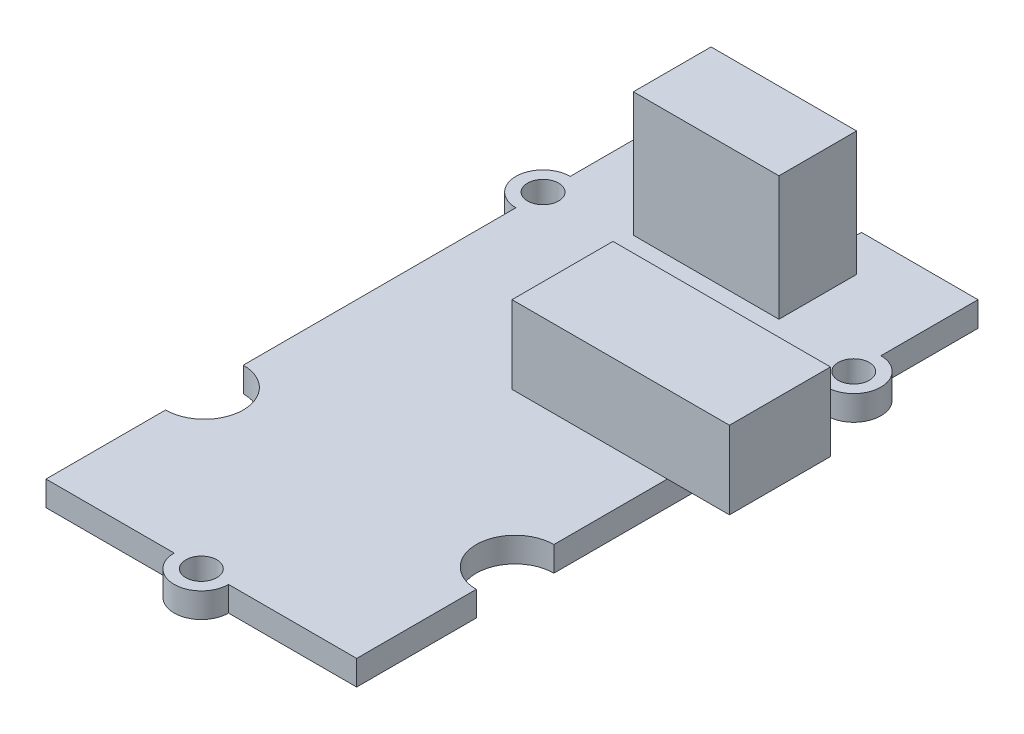
SolidWorks part; units mm, degrees
ref_plane "Front Plane" through (0, 0, 0) normal (0, 0, 1) x (1, 0, 0)
ref_plane "Top Plane" through (0, 0, 0) normal (0, 1, 0) x (1, 0, 0)
ref_plane "Right Plane" through (0, 0, 0) normal (1, 0, 0) x (0, 0, -1)
sketch "Sketch1" plane through (0, 0, 0) normal (0, 1, 0) x (1, 0, 0)
  line L0 (0, 20) -> (0, -20) construction
  line L1 (-10, -20) -> (10, -20)
  line L2 (-10, -20) -> (-10, 20)
  line L3 (-10, 20) -> (10, 20)
  line L4 (10, -20) -> (10, 20)
  line L5 (-10, -20) -> (10, 20) construction
  line L6 (-10, 20) -> (10, -20) construction
  circle A0 centre (10, 12) radius 1
  circle A1 centre (10, 12) radius 1.75
  circle A2 centre (-10, 12) radius 1.75
  circle A3 centre (-10, 12) radius 1
  circle A4 centre (0, -20) radius 1
  circle A5 centre (0, -20) radius 1.75
  circle A6 centre (10, -9.8) radius 2.5
  circle A7 centre (-10, -9.8) radius 2.5
  circle A8 centre (0, 20) radius 2.5
  point P0 (0, 0)
  point P25 (0, 0)
  point P26 (0, 20.0134)
  dimension "D3" = 2
  dimension "D4" = 0.75
  dimension "D5" = 8
  dimension "D6" = 2
  dimension "D8" = 5
  dimension "D9" = 10.2
  dimension "D10" = 5
  dimension "D1" = 40
  dimension "D2" = 20
  dimension "D7" = 0.75
extrude "PCB" add sketch "Sketch1" along normal blind 1.6 contours A8 L3 L2 A2 A7 L1 A5 L4 A6 A1 | L1 A5 A4 | L1 A5 A4 | L4 A1 A0 | L4 A1 A0 | L2 A3 A2 | L2 A3 A2 region at (0, 0, 18.9609) region at (1.375, 0, 20.0391) region at (0, 0, 0.0216) region at (8.2891, 0, -12) region at (10.0391, 0, -10.625) region at (-11.7109, 0, -12) region at (-9.9609, 0, -10.625)
sketch "Sketch2" plane through (0, 1.6, 0) normal (0, 1, 0) x (1, 0, 0)
  line L0 (10, -7.3) -> (10, 10.25) construction
  line L1 (0, 6.5) -> (14, 6.5)
  line L2 (0, 6.5) -> (0, 0)
  line L3 (0, 0) -> (14, 0)
  line L4 (14, 6.5) -> (14, 0)
  line L5 (2.5, 20) -> (10, 20) construction
  line L6 (0, 20) -> (0, -21.75) construction
  line L8 (-4.6845, 17.5) -> (4.6845, 17.5)
  line L9 (-4.6845, 17.5) -> (-4.6845, 12.5)
  line L10 (-4.6845, 12.5) -> (4.6845, 12.5)
  line L11 (4.6845, 17.5) -> (4.6845, 12.5)
  arc A0 (-1.75, -20) -> (1.75, -20) centre (0, -20) ccw construction
  arc A1 (-2.5, 20) -> (2.5, 20) centre (0, 20) ccw construction
  point P20 (0, 0)
  point P22 (0, 17.5)
  line M17 (10, -7.3) -> (10, 10.25)
  dimension "D1" = 6.5
  dimension "D2" = 14
  dimension "D3" = 10
  dimension "D4" = 20
  dimension "D5" = 5
  dimension "D6" = 9.369
extrude "Electrode_connector" add sketch "Sketch2" along normal blind 5 contours L2 L3 L1 M17 | L4 L1 L3 M17 region at (5, 1.6, -3.25) region at (12, 1.6, -3.25)
extrude "Control_connector" add sketch "Sketch2<3>" along normal blind 8 contours L6 L8 L9 L10 | L8 L6 L10 L11 region at (-2.3423, 1.6, -15) region at (2.3423, 1.6, -15)
sketch "Sketch2<3>" plane through (0, 1.6, 0) normal (0, 1, 0) x (1, 0, 0) same geometry as "Sketch2"
